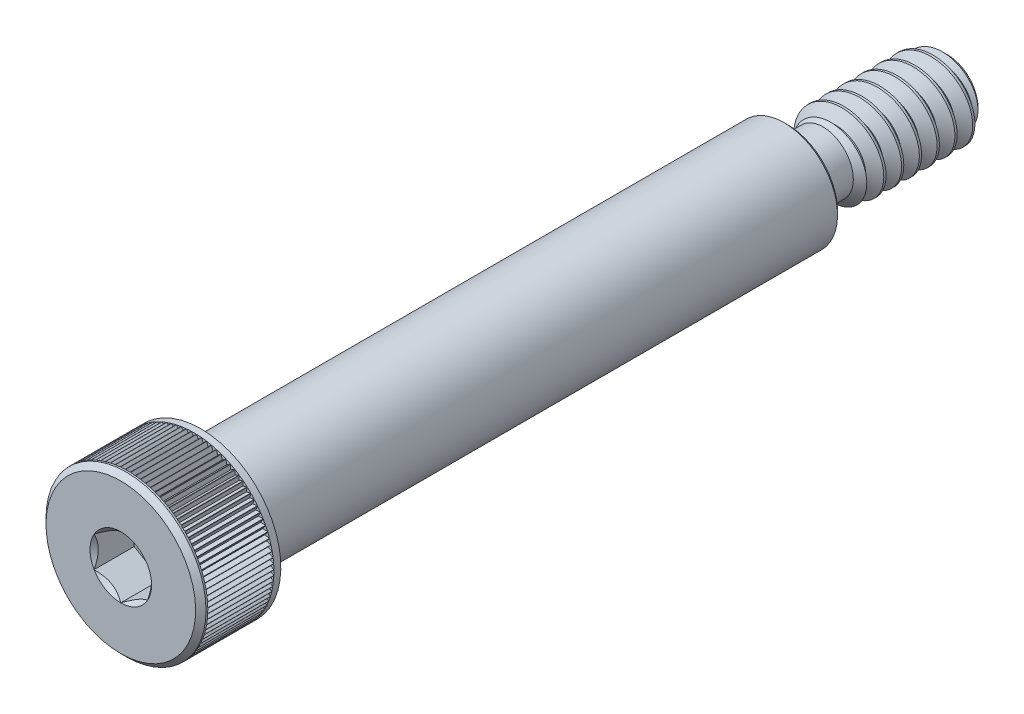
SolidWorks part; units mm, degrees
ref_plane "Front" through (0, 0, 0) normal (0, 0, 1) x (1, 0, 0)
ref_plane "Top" through (0, 0, 0) normal (0, 1, 0) x (1, 0, 0)
ref_plane "Right" through (0, 0, 0) normal (1, 0, 0) x (0, 0, -1)
sketch "Sketch1" plane through (0, 0, 0) normal (1, 0, 0) x (0, 0, -1)
  line L0 (0, 4.7625) -> (4.7625, 4.7625)
  line L1 (4.7625, 4.7625) -> (4.7625, 3.175)
  line L2 (4.7625, 3.175) -> (39.6875, 3.175)
  line L3 (39.6875, 3.175) -> (39.6875, 2.413)
  line L4 (39.6875, 2.413) -> (49.2125, 2.413)
  line L5 (49.2125, 2.413) -> (49.2125, 0)
  line L6 (49.2125, 0) -> (0, 0)
  line L7 (0, 0) -> (0, 4.7625)
  line L8 (0, 4.7625) -> (0, -4.7625) construction
  line L9 (49.2125, 2.413) -> (49.2125, -2.413) construction
  line L10 (39.6875, 3.175) -> (39.6875, -3.175) construction
  line L11 (49.2125, -2.413) -> (47.5347, -2.413) construction
  line L12 (22.225, 0) -> (22.225, 3.175) construction
  point P8 (47.625, -2.413)
  point P12 (39.6875, 0)
  point P17 (8.255, 3.175)
  point P18 (22.225, 0)
  point P19 (22.225, 3.175)
  point P20 (36.195, 3.175)
  point P21 (36.195, -3.175)
  point P22 (8.255, -3.175)
  dimension "Head Dia" = 9.525
  dimension "Head Ht" = 4.7625
  dimension "Thread Lg" = 9.525
  dimension "Thread Dia" = 4.826
  dimension "Shoulder Dia" = 6.35
  dimension "Shoulder Lg" = 34.925
  dimension "D1" = 1.5875
  dimension "D2" = 1.6778
  dimension "D3" = 17.4625
  dimension "D4" = 3.4925
revolve "Revolve1" add sketch "Sketch1" angle 360 mid plane about L6
ref_plane "Plane1" through (0, 0, -49.2125) normal (0, 0, 1) x (1, 0, 0)
sketch "Sketch3" plane through (0, 0, -49.2125) normal (0, 0, 1) x (1, 0, 0)
  circle A0 centre (0, 0) radius 2.413
sketch "Sketch5" plane through (0, 0, 0) normal (1, 0, 0) x (0, 0, -1)
  line L0 (39.6875, 3.175) -> (43.1673, 3.175)
  line L1 (43.1673, 3.175) -> (41.7957, 1.8034)
  line L2 (41.7957, 1.8034) -> (40.2971, 1.8034)
  line L3 (39.6875, 3.175) -> (39.6875, 2.413)
  line L5 (39.6875, 2.413) -> (49.2125, 2.413) construction
  line L6 (49.2125, 0) -> (41.7957, 0) construction
  line L7 (45.5041, 0) -> (45.5041, -2.413) construction
  arc A0 (39.6875, 2.413) -> (40.2971, 1.8034) centre (40.2971, 2.413) ccw
  dimension "D1" = 45
  dimension "CADB" = 2.1082
  dimension "CADA" = 3.6068
revolve "Cut-Revolve1" cut sketch "Sketch5" angle 360 mid plane about L6
chamfer "Chamfer1" distance 0.6032 angle 45 1 edges at (0, 2.413, -49.2125)
chamfer "Chamfer2" distance 0.3096 angle 45 1 edges at (0, 4.7625, 0)
chamfer "Chamfer3" distance 0.2032 angle 45 1 edges at (0, 3.175, -39.6875)
sketch "Sketch10" plane through (0, 0, 0) normal (1, 0, 0) x (0, 0, -1)
  line L0 (0.3096, 0) -> (4.4529, 0) construction
  line L1 (0.3096, -4.7625) -> (0.3096, 4.7625) construction
  line L3 (0.3096, 0) -> (0, 0) construction
  line L4 (4.4529, 0) -> (4.7625, 0) construction
  line L5 (4.7625, -4.7625) -> (4.7625, 4.7625) construction
  point P6 (2.3812, 0)
  dimension "D1" = 4.1434
ref_plane "Plane2" through (0, 0, -2.3812) normal (0, 0, 1) x (1, 0, 0)
sketch "Sketch11" plane through (0, 0, -2.3812) normal (0, 0, 1) x (1, 0, 0)
  line L0 (0, 4.5148) -> (0, 4.7625) construction
  line L1 (0, 4.5148) -> (0.143, 4.7625)
  line L2 (0, 4.5148) -> (-0.143, 4.7625)
  line L3 (-0.143, 4.7625) -> (0.143, 4.7625)
  line L4 (0, 0) -> (-0.143, 4.7625) construction
  line L5 (0.143, 4.7625) -> (0, 0) construction
  circle A1 centre (0, 0) radius 4.7625 construction
  circle A2 centre (0, 0) radius 4.5148 construction
  circle A3 centre (0, 0) radius 4.4529 construction
  point P3 (0, 0.0018)
  point P8 (2.3908, 0.7309)
  dimension "D1" = 0.2476
  dimension "D2" = 3.439
extrude "Cut-Extrude5" cut sketch "Sketch11" against normal mid plane 3.9362
pattern_circular "CirPattern1" count 99 over 360 about axis through (0, 0, -49.2125) along (0, 0, -1) of "Cut-Extrude5"
sketch "Sketch8" plane through (0, 0, 0) normal (0, 0, 1) x (1, 0, 0)
  line L1 (1.5875, 0.9165) -> (0, 1.8331)
  line L2 (0, 1.8331) -> (-1.5875, 0.9165)
  line L3 (-1.5875, 0.9165) -> (-1.5875, -0.9165)
  line L4 (-1.5875, -0.9165) -> (0, -1.8331)
  line L5 (0, -1.8331) -> (1.5875, -0.9165)
  line L6 (1.5875, -0.9165) -> (1.5875, 0.9165)
  circle A0 centre (0, 0) radius 1.5875 construction
  dimension "Hex" = 3.175
extrude "Cut-Extrude2" cut sketch "Sketch8" against normal blind 2.3813
sketch "Sketch9" plane through (0, 0, 0) normal (0, 0, 1) x (1, 0, 0)
  circle A0 centre (0, 0) radius 1.8331
extrude "Cut-Extrude4" cut sketch "Sketch9" against normal blind 2.3813 draft 45
sketch "Front Sketch" plane through (0, 0, 0) normal (0, 0, 1) x (1, 0, 0)
  line L0 (1.5875, -0.9165) -> (1.5875, 0.9165) construction
  line L1 (-1.5875, 0.9165) -> (-1.5875, -0.9165) construction
  circle A0 centre (0, 0) radius 4.7625 construction
  point P4 (-1.5875, 0)
  point P5 (1.5875, 0)
  point P6 (4.7625, 0)
  point P9 (-4.7625, 0)
ref_plane "Contact Plane 1" through (0, 0, -4.7625) normal (0, 0, -1) x (-1, 0, 0)
ref_axis "Center Axis 1" through (0, 0, -49.2125) along (0, 0, 1)
curve "Helix/Spiral1" pitch 1.0583 height 10.5833 radius 2.413 centre (0, 0, -49.2125) axis (0, 0, 1) start towards (0, 1, 0)
sketch "Sketch4" plane through (0, 0, 0) normal (1, 0, 0) x (0, 0, -1)
  line L0 (49.1464, 2.5276) -> (50.2047, 2.5276) construction
  line L1 (50.2047, 2.5276) -> (49.6755, 1.611) construction
  line L3 (49.6755, 1.611) -> (49.1464, 2.5276) construction
  line L4 (49.1794, 2.4703) -> (50.1716, 2.4703) construction
  line L5 (49.2125, 2.413) -> (50.1385, 2.413) construction
  line L6 (49.6094, 1.7256) -> (49.7417, 1.7256) construction
  line L7 (49.6755, 1.7256) -> (49.6755, 1.611) construction
  line L8 (49.6755, 2.5276) -> (49.6755, 2.413) construction
  line L9 (49.1794, 2.4703) -> (50.1716, 2.4703)
  line L10 (50.1716, 2.4703) -> (49.7417, 1.7256)
  line L11 (49.7417, 1.7256) -> (49.6094, 1.7256)
  line L12 (49.6094, 1.7256) -> (49.1794, 2.4703)
  point P14 (49.6755, 2.4703)
  point P15 (49.6755, 2.5276)
  dimension "D1" = 1.0583
  dimension "D2" = 0.1323
sweep "Cut-Sweep1" cut profiles "Sketch4" path "Helix/Spiral1" align with end faces yes
sketch "Sketch12" plane through (0, 0, 0) normal (1, 0, 0) x (0, 0, -1)
  line L1 (39.6875, 2.9718) -> (39.4843, 3.175)
  line L2 (39.4843, 3.175) -> (4.7625, 3.175)
  line L3 (4.7625, 3.175) -> (4.7625, 0)
  line L4 (4.7625, -4.7625) -> (4.7625, 4.7625) construction
  line L5 (4.7625, 0) -> (39.6875, 0)
  line L6 (39.6875, 2.9718) -> (39.6875, 2.413)
  line L7 (41.7957, 1.8034) -> (40.2971, 1.8034) construction
  line L8 (41.7957, 1.8034) -> (40.2971, 1.8034)
  line L9 (41.7957, 1.8034) -> (41.7957, 0)
  line L10 (41.7957, 0) -> (39.6875, 0)
  arc A0 (39.6875, 2.413) -> (40.2971, 1.8034) centre (40.2971, 2.413) ccw construction
  arc A1 (39.6875, 2.413) -> (40.2971, 1.8034) centre (40.2971, 2.413) ccw
revolve "Revolve2" add sketch "Sketch12" angle 360 about L5
equation "\"D3@Helix/Spiral1\" = \"Thread Lg@Sketch1\" + \"D4@Helix/Spiral1\""
equation "\"D1@Chamfer1\" = \"Thread Dia@Sketch1\" * .125"
equation "\"D1@Cut-Extrude2\"= \"Head Ht@Sketch1\" * .5"
equation "\"D1@Cut-Extrude4\" = \"D1@Cut-Extrude2\""
equation "\"D1@Chamfer2\" = \"Head Dia@Sketch1\" * .0325"
equation "\"D1@Sketch1\"=\"D4@Helix/Spiral1\"*1.5"
equation "\"D1@Sketch11\"=\"D1@Chamfer2\"*.8"
equation "\"D1@Cut-Extrude5\"=\"D1@Sketch10\"*.95"
equation "\"D1@CirPattern1\"=(360/\"D2@Sketch11\")-6"
equation "\"D3@Sketch1\"=\"Shoulder Lg@Sketch1\"/2"
equation "\"D4@Sketch1\"=\"D3@Sketch1\"*.2"
equation "\"D1@Sketch4\"=\"D4@Helix/Spiral1\""
equation "\"D2@Sketch4\"=\"D1@Sketch4\"/8"
